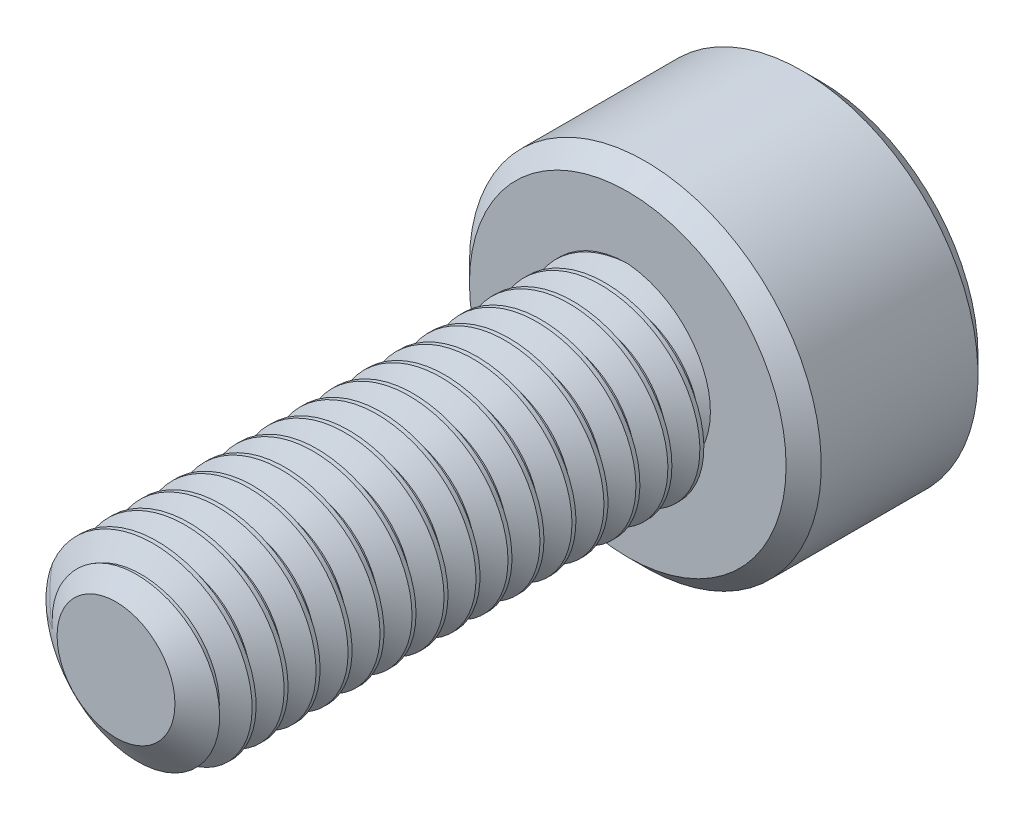
SolidWorks part; units mm, degrees
ref_plane "Front Plane" through (0, 0, 0) normal (0, 0, 1) x (1, 0, 0)
ref_plane "Top Plane" through (0, 0, 0) normal (0, 1, 0) x (1, 0, 0)
ref_plane "Right Plane" through (0, 0, 0) normal (1, 0, 0) x (0, 0, -1)
sketch "Sketch1" plane through (0, 0, 0) normal (0, 0, 1) x (1, 0, 0)
  circle A0 centre (0, 0) radius 1.5
  dimension "OD" = 3
extrude "Extrude1" add sketch "Sketch1" against normal blind 8
sketch "Sketch2" plane through (0, 0, 0) normal (0, 0, 1) x (1, 0, 0)
  circle A0 centre (0, 0) radius 1.5 construction
  circle A1 centre (0, 0) radius 1.5
curve "Helix/Spiral1" pitch 0.5 height 8.5 radius 1.5 centre (0, 0, 0) axis (0, 0, -1) start towards (0, 1, 0) parameters "pitch"=0.5
sketch "Sketch3" plane through (0, 0, 0) normal (1, 0, 0) x (0, 0, -1)
  line L0 (-0.4375, 1.5) -> (-0.25, 1.1752)
  line L1 (-0.25, 1.1752) -> (-0.1875, 1.1752)
  line L2 (-0.1875, 1.1752) -> (0, 1.5)
  line L3 (-0.4375, 1.5) -> (0, 1.5)
  line L4 (-0.2187, 1.5) -> (-0.2188, 1.1752) construction
  line L5 (-0.3438, 1.3376) -> (-0.0938, 1.3376) construction
  line L6 (0, 1.5) -> (0, -1.5) construction
  dimension "D1" = 0.0625
  dimension "D2" = 0.25
  dimension "D3" = 60
sweep "Cut-Sweep1" cut profiles "Sketch3" path "Helix/Spiral1"
sketch "Sketch4" plane through (0, 0, 0) normal (1, 0, 0) x (0, 0, -1)
  line L0 (0.4053, 1.5) -> (0, 0.9212)
  line L1 (0, 0.9212) -> (0, 1.5)
  line L2 (0.4053, 1.5) -> (0, 1.5)
  line L3 (-0.4375, 1.5) -> (0, 1.5) construction
  line L4 (0, 0) -> (7.0209, 0) construction
  dimension "D1" = 55
  dimension "D2" = 0.254
revolve "Cut-Revolve1" cut sketch "Sketch4" angle 360 about L4
sketch "Sketch6" plane through (0, 0, -8) normal (0, 0, -1) x (-1, 0, 0)
  circle A0 centre (0, 0) radius 2.75
  dimension "head dia" = 5.5
extrude "Extrude2" add sketch "Sketch6" along normal blind 3
sketch "Sketch7" plane through (0, 0, -11) normal (0, 0, -1) x (-1, 0, 0)
  line L1 (0, 1.4434) -> (-1.25, 0.7217)
  line L2 (-1.25, 0.7217) -> (-1.25, -0.7217)
  line L3 (-1.25, -0.7217) -> (0, -1.4434)
  line L4 (0, -1.4434) -> (1.25, -0.7217)
  line L5 (1.25, -0.7217) -> (1.25, 0.7217)
  line L6 (1.25, 0.7217) -> (0, 1.4434)
  circle A0 centre (0, 0) radius 1.25 construction
  dimension "hex dia" = 2.5
extrude "Cut-Extrude1" cut sketch "Sketch7" against normal blind 1.875
sketch "Sketch8" plane through (0, 0, -11) normal (0, 0, -1) x (-1, 0, 0)
  circle A0 centre (0, 0) radius 1.4434
extrude "Cut-Extrude2" cut sketch "Sketch8" against normal through all draft 45
chamfer "Chamfer1" distance 0.275 angle 45 2 edges at (-2.75, 0, -11) (-2.75, 0, -8)
sketch "Sketch10" plane through (0, 0, -8) normal (0, 0, 1) x (1, 0, 0)
  circle A1 centre (0, 0) radius 1.5
  circle A2 centre (0, 0) radius 1.5
  dimension "D1" = 0
ref_plane "Plane1" through (0, 0, 0) normal (0, 0, 1) x (1, 0, 0)
extrude "partial thread" [suppressed] add sketch "Sketch10" along normal up to surface (4 mm away) separate body up to plane "Plane1"
chamfer "Chamfer2" [suppressed] distance 0.06 angle 45
combine bodies "Combine1" [suppressed] operation type add bodies to combine 107 108
sketch "Sketch9" plane through (0, 0, 0) normal (1, 0, 0) x (0, 0, -1)
  line L0 (0, 1.5) -> (0, -1.5) construction
  line L1 (1.25, 1.5) -> (1.25, -1.5) construction
  dimension "D1" = 1.25
equation "\"D3@Helix/Spiral1\" = \"screw length@Extrude1\"+\"pitch@Helix/Spiral1\""
equation "\"D1@Sketch3\" = \"pitch@Helix/Spiral1\"*.125"
equation "\"D2@Sketch3\" = \"pitch@Helix/Spiral1\"*.5"
equation "\"D1@Cut-Extrude1\" = \"hex dia@Sketch7\"*.75"
equation "\"D1@Chamfer1\" = \"head dia@Sketch6\"*.05"
equation "\"D1@Sketch9\" = \"pitch@Helix/Spiral1\"*2.5"
equation "\"D1@Chamfer2\"=\"OD@Sketch1\"*.02"
